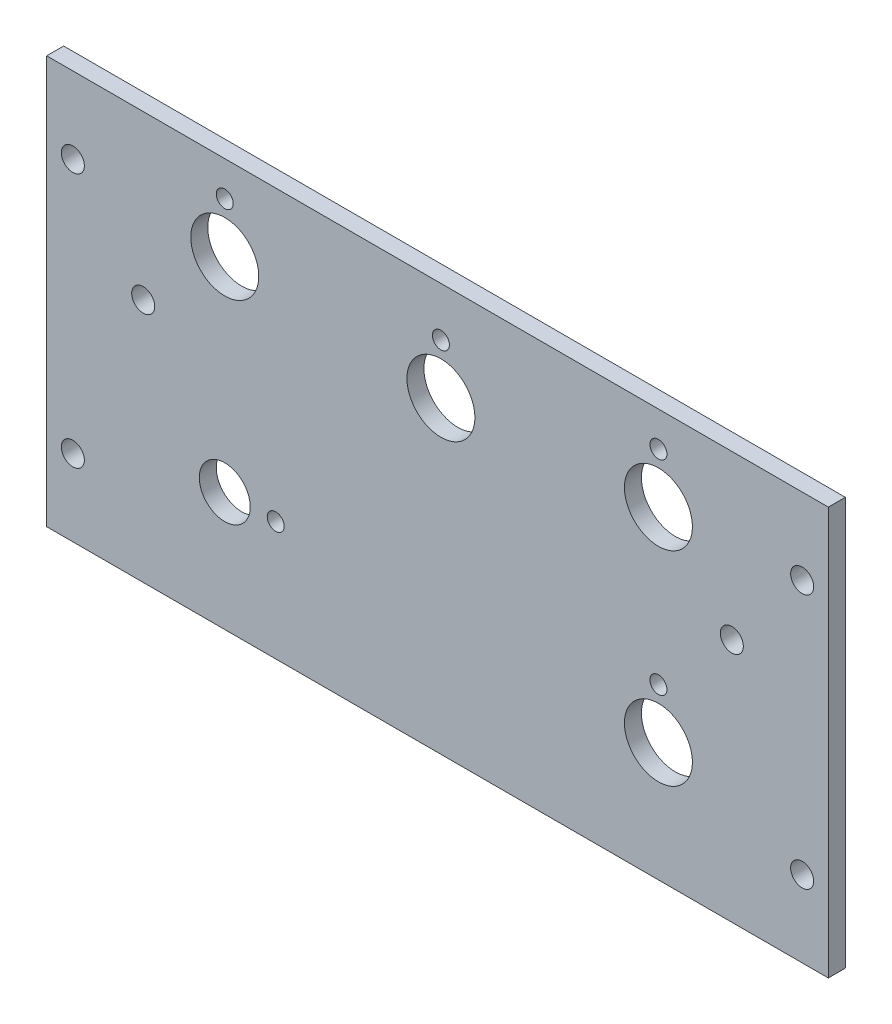
SolidWorks part; units mm, degrees
ref_plane "Front Plane" through (0, 0, 0) normal (0, 0, 1) x (1, 0, 0)
ref_plane "Top Plane" through (0, 0, 0) normal (0, 1, 0) x (1, 0, 0)
ref_plane "Right Plane" through (0, 0, 0) normal (1, 0, 0) x (0, 0, -1)
sketch "Sketch1" plane through (0, 0, 0) normal (0, 0, 1) x (1, 0, 0)
  line L4 (0, 76.2) -> (-146.05, 76.2)
  line L5 (-146.05, 76.2) -> (-146.05, 0)
  line L6 (-146.05, 0) -> (0, 0)
  line L7 (0, 0) -> (0, 76.2)
  line L8 (0, 76.2) -> (-146.05, 76.2)
  line L9 (-146.05, 76.2) -> (-146.05, 0)
  line L10 (-146.05, 0) -> (0, 0)
  line L11 (0, 0) -> (0, 76.2)
  dimension "D1" = 0
extrude "Boss-Extrude1" add sketch "Sketch1" against normal blind 3.175
hole_wizard "#6 Clearance Hole1" positions "Sketch3" profile "Sketch2" hole size "#6" standard "ANSI Inch" end condition through all
sketch "Sketch3" plane through (0, 0, -3.175) normal (0, 0, -1) x (-1, 0, 0)
  point P0 (4.8895, 61.9125)
  point P3 (4.8895, 14.2875)
  point P6 (141.1605, 14.2875)
  point P9 (141.1605, 61.9125)
  point P12 (128.016, 45.72)
  point P15 (18.034, 45.72)
sketch "Sketch2" plane through (-4.8895, 61.9125, -3.175) normal (1, 0, 0) x (0, 1, 0)
  line L0 (0, 0) -> (0, 3.175)
  line L1 (0, 3.175) -> (2.1526, 3.175)
  line L2 (2.1526, 3.175) -> (2.1526, 0)
  line L5 (2.1526, 0) -> (0, 0)
  line L11 (0, -6.35) -> (0, 107.95) construction
  dimension "Thru Hole Dia." = 4.3053
  dimension "Thru Hole Depth" = 3.175
hole_wizard "3/8 (0.375) Diameter Hole1" positions "Sketch7" profile "Sketch6" hole size "3/8" standard "ANSI Inch" end condition through all
sketch "Sketch7" plane through (0, 0, -3.175) normal (0, 0, -1) x (-1, 0, 0)
  line L0 (0, 0) -> (0, 76.2) construction
  line L1 (0, 76.2) -> (146.05, 76.2) construction
  point P3 (112.776, 22.225)
  dimension "D1" = 112.776
  dimension "D2" = 53.975
sketch "Sketch6" plane through (-112.776, 22.225, -3.175) normal (1, 0, 0) x (0, 1, 0)
  line L0 (0, 0) -> (0, 3.175)
  line L1 (0, 3.175) -> (4.7625, 3.175)
  line L2 (4.7625, 3.175) -> (4.7625, 0)
  line L5 (4.7625, 0) -> (0, 0)
  line L11 (0, -6.35) -> (0, 107.95) construction
  dimension "Thru Hole Dia." = 9.525
  dimension "Thru Hole Depth" = 3.175
hole_wizard "1/2 (0.5) Diameter Hole1" positions "Sketch5" profile "Sketch4" hole size "1/2" standard "ANSI Inch" end condition through all
sketch "Sketch5" plane through (0, 0, -3.175) normal (0, 0, -1) x (-1, 0, 0)
  line L0 (0, 0) -> (0, 76.2) construction
  line L1 (0, 76.2) -> (146.05, 76.2) construction
  line L2 (0, 38.1) -> (146.05, 38.1) construction
  line L3 (146.05, 76.2) -> (146.05, 0) construction
  line L5 (112.776, 22.225) -> (31.75, 22.225) construction
  point P0 (31.75, 60.325)
  point P3 (72.39, 57.658)
  point P6 (112.776, 60.325)
  point P29 (31.75, 22.225)
  dimension "D1" = 31.75
  dimension "D2" = 15.875
  dimension "D3" = 2.667
  dimension "D4" = 40.64
  dimension "D5" = 81.026
sketch "Sketch4" plane through (-31.75, 60.325, -3.175) normal (1, 0, 0) x (0, 1, 0)
  line L0 (0, 0) -> (0, 3.175)
  line L1 (0, 3.175) -> (6.35, 3.175)
  line L2 (6.35, 3.175) -> (6.35, 0)
  line L5 (6.35, 0) -> (0, 0)
  line L11 (0, -6.35) -> (0, 107.95) construction
  dimension "Thru Hole Dia." = 12.7
  dimension "Thru Hole Depth" = 3.175
hole_wizard "1/8 (0.125) Diameter Hole1" positions "Sketch9" profile "Sketch8" hole size "1/8" standard "ANSI Inch" end condition through all
sketch "Sketch9" plane through (0, 0, -3.175) normal (0, 0, -1) x (-1, 0, 0)
  line L0 (31.75, 69.6995) -> (31.75, 60.325) construction
  line L2 (72.39, 57.658) -> (72.39, 67.0325) construction
  line L4 (112.776, 60.325) -> (112.776, 69.6995) construction
  line L6 (31.75, 22.225) -> (31.75, 31.5995) construction
  line L8 (72.39, 19.558) -> (72.39, 28.9325) construction
  point P0 (31.75, 69.6995)
  point P2 (112.776, 69.6995)
  point P4 (103.251, 22.225)
  point P14 (72.39, 67.0325)
  point P23 (31.75, 31.5995)
  dimension "D1" = 9.3745
sketch "Sketch8" plane through (-31.75, 69.6995, -3.175) normal (1, 0, 0) x (0, 1, 0)
  line L0 (0, 0) -> (0, 3.175)
  line L1 (0, 3.175) -> (1.5875, 3.175)
  line L2 (1.5875, 3.175) -> (1.5875, 0)
  line L5 (1.5875, 0) -> (0, 0)
  line L11 (0, -6.35) -> (0, 107.95) construction
  dimension "Thru Hole Dia." = 3.175
  dimension "Thru Hole Depth" = 3.175
